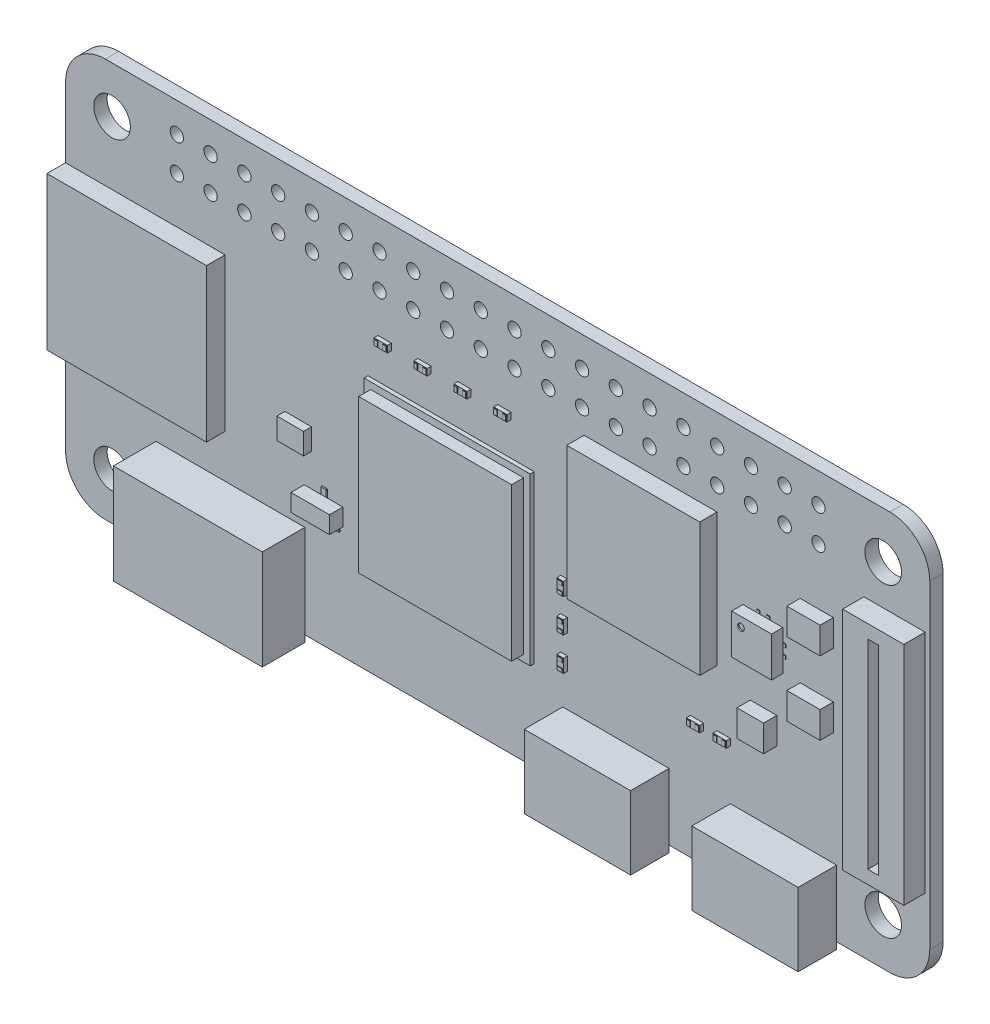
SolidWorks part; units mm, degrees
ref_plane "Front Plane" through (0, 0, 0) normal (0, 0, 1) x (1, 0, 0)
ref_plane "Top Plane" through (0, 0, 0) normal (0, 1, 0) x (1, 0, 0)
ref_plane "Right Plane" through (0, 0, 0) normal (1, 0, 0) x (0, 0, -1)
sketch "Sketch1" plane through (0, 0, 0) normal (0, 0, 1) x (1, 0, 0)
  line L0 (3, 0) -> (62, 0)
  line L1 (65, 3) -> (65, 27)
  line L2 (62, 30) -> (3, 30)
  line L3 (0, 27) -> (0, 3)
  arc A0 (62, 0) -> (65, 3) centre (62, 3) ccw
  arc A1 (65, 27) -> (62, 30) centre (62, 27) ccw
  arc A2 (3, 30) -> (0, 27) centre (3, 27) ccw
  arc A3 (0, 3) -> (3, 0) centre (3, 3) ccw
extrude "PCB" add sketch "Sketch1" along normal blind 1
ref_plane "Plane_z1" through (0, 0, 1) normal (0, 0, 1) x (1, 0, 0)
sketch "Sketch2" plane through (0, 0, 1) normal (0, 0, 1) x (1, 0, 0)
  line L1 (52, 15.3) -> (52.25, 15.3)
  line L2 (52, 15.3) -> (52, 15.6)
  line L3 (52, 15.6) -> (52.25, 15.6)
  line L4 (52.25, 15.3) -> (52.25, 15.6)
  line L6 (50.8, 16.5) -> (51.1, 16.5)
  line L7 (50.8, 16.5) -> (50.8, 16.75)
  line L8 (50.8, 16.75) -> (51.1, 16.75)
  line L9 (51.1, 16.5) -> (51.1, 16.75)
  line L11 (52, 18.4) -> (52.25, 18.4)
  line L12 (52, 18.4) -> (52, 18.7)
  line L13 (52, 18.7) -> (52.25, 18.7)
  line L14 (52.25, 18.4) -> (52.25, 18.7)
  line L16 (53.9, 16.5) -> (54.2, 16.5)
  line L17 (53.9, 16.5) -> (53.9, 16.75)
  line L18 (53.9, 16.75) -> (54.2, 16.75)
  line L19 (54.2, 16.5) -> (54.2, 16.75)
  line L21 (52.75, 15.3) -> (53, 15.3)
  line L22 (52.75, 15.3) -> (52.75, 15.6)
  line L23 (52.75, 15.6) -> (53, 15.6)
  line L24 (53, 15.3) -> (53, 15.6)
  line L26 (50.8, 17.25) -> (51.1, 17.25)
  line L27 (50.8, 17.25) -> (50.8, 17.5)
  line L28 (50.8, 17.5) -> (51.1, 17.5)
  line L29 (51.1, 17.25) -> (51.1, 17.5)
  line L31 (52.75, 18.4) -> (53, 18.4)
  line L32 (52.75, 18.4) -> (52.75, 18.7)
  line L33 (52.75, 18.7) -> (53, 18.7)
  line L34 (53, 18.4) -> (53, 18.7)
  line L36 (53.9, 17.25) -> (54.2, 17.25)
  line L37 (53.9, 17.25) -> (53.9, 17.5)
  line L38 (53.9, 17.5) -> (54.2, 17.5)
  line L39 (54.2, 17.25) -> (54.2, 17.5)
extrude "SMD_add00" add sketch "Sketch2" along normal blind 0.05
sketch "Sketch3" plane through (0, 0, 1) normal (0, 0, 1) x (1, 0, 0)
  line L1 (18.35, 8.05) -> (18.75, 8.05)
  line L2 (18.35, 8.05) -> (18.35, 8.75)
  line L3 (18.35, 8.75) -> (18.75, 8.75)
  line L4 (18.75, 8.05) -> (18.75, 8.75)
  line L6 (20.25, 8.05) -> (20.65, 8.05)
  line L7 (20.25, 8.05) -> (20.25, 8.75)
  line L8 (20.25, 8.75) -> (20.65, 8.75)
  line L9 (20.65, 8.05) -> (20.65, 8.75)
  line L11 (19.3, 9.65) -> (19.7, 9.65)
  line L12 (19.3, 9.65) -> (19.3, 10.35)
  line L13 (19.3, 10.35) -> (19.7, 10.35)
  line L14 (19.7, 9.65) -> (19.7, 10.35)
extrude "SMD_add01" add sketch "Sketch3" along normal blind 0.1
sketch "Sketch4" plane through (0, 0, 1) normal (0, 0, 1) x (1, 0, 0)
  line L1 (22.75, 6.75) -> (35.25, 6.75)
  line L2 (22.75, 6.75) -> (22.75, 19.25)
  line L3 (22.75, 19.25) -> (35.25, 19.25)
  line L4 (35.25, 6.75) -> (35.25, 19.25)
  line L6 (37.25, 7.5) -> (37.75, 7.5)
  line L7 (37.25, 7.5) -> (37.25, 8.5)
  line L8 (37.25, 8.5) -> (37.75, 8.5)
  line L9 (37.75, 7.5) -> (37.75, 8.5)
  line L11 (37.25, 10) -> (37.75, 10)
  line L12 (37.25, 10) -> (37.25, 11)
  line L13 (37.25, 11) -> (37.75, 11)
  line L14 (37.75, 10) -> (37.75, 11)
  line L16 (37.25, 12.5) -> (37.75, 12.5)
  line L17 (37.25, 12.5) -> (37.25, 13.5)
  line L18 (37.25, 13.5) -> (37.75, 13.5)
  line L19 (37.75, 12.5) -> (37.75, 13.5)
  line L21 (47, 8.75) -> (48, 8.75)
  line L22 (47, 8.75) -> (47, 9.25)
  line L23 (47, 9.25) -> (48, 9.25)
  line L24 (48, 8.75) -> (48, 9.25)
  line L26 (49, 8.75) -> (50, 8.75)
  line L27 (49, 8.75) -> (49, 9.25)
  line L28 (49, 9.25) -> (50, 9.25)
  line L29 (50, 8.75) -> (50, 9.25)
  line L31 (23.5, 21.75) -> (24.5, 21.75)
  line L32 (23.5, 21.75) -> (23.5, 22.25)
  line L33 (23.5, 22.25) -> (24.5, 22.25)
  line L34 (24.5, 21.75) -> (24.5, 22.25)
  line L36 (26.5, 21.75) -> (27.5, 21.75)
  line L37 (26.5, 21.75) -> (26.5, 22.25)
  line L38 (26.5, 22.25) -> (27.5, 22.25)
  line L39 (27.5, 21.75) -> (27.5, 22.25)
  line L41 (29.5, 21.75) -> (30.5, 21.75)
  line L42 (29.5, 21.75) -> (29.5, 22.25)
  line L43 (29.5, 22.25) -> (30.5, 22.25)
  line L44 (30.5, 21.75) -> (30.5, 22.25)
  line L46 (32.5, 21.75) -> (33.5, 21.75)
  line L47 (32.5, 21.75) -> (32.5, 22.25)
  line L48 (32.5, 22.25) -> (33.5, 22.25)
  line L49 (33.5, 21.75) -> (33.5, 22.25)
extrude "SMD_add02" add sketch "Sketch4" along normal blind 0.3
sketch "Sketch5" plane through (0, 0, 1) normal (0, 0, 1) x (1, 0, 0)
  line L1 (16.5, 12.2) -> (18.5, 12.2)
  line L2 (16.5, 12.2) -> (16.5, 13.8)
  line L3 (16.5, 13.8) -> (18.5, 13.8)
  line L4 (18.5, 12.2) -> (18.5, 13.8)
extrude "SMD_add03" add sketch "Sketch5" along normal blind 0.6
sketch "Sketch6" plane through (0, 0, 1) normal (0, 0, 1) x (1, 0, 0)
  line L1 (55.25, 19) -> (57.75, 19)
  line L2 (55.25, 19) -> (55.25, 21)
  line L3 (55.25, 21) -> (57.75, 21)
  line L4 (57.75, 19) -> (57.75, 21)
  line L6 (55.25, 13.5) -> (57.75, 13.5)
  line L7 (55.25, 13.5) -> (55.25, 15.5)
  line L8 (55.25, 15.5) -> (57.75, 15.5)
  line L9 (57.75, 13.5) -> (57.75, 15.5)
  line L11 (51.5, 10.5) -> (53.5, 10.5)
  line L12 (51.5, 10.5) -> (51.5, 12.5)
  line L13 (51.5, 12.5) -> (53.5, 12.5)
  line L14 (53.5, 10.5) -> (53.5, 12.5)
extrude "SMD_add04" add sketch "Sketch6" along normal blind 1
sketch "Sketch7" plane through (0, 0, 1) normal (0, 0, 1) x (1, 0, 0)
  line L1 (39, 13.5) -> (49, 13.5)
  line L2 (39, 13.5) -> (39, 23.5)
  line L3 (39, 23.5) -> (49, 23.5)
  line L4 (49, 13.5) -> (49, 23.5)
extrude "SMD_add05" add sketch "Sketch7" along normal blind 1.3
sketch "Sketch8" plane through (0, 0, 1) normal (0, 0, 1) x (1, 0, 0)
  line L1 (0, 10.25) -> (12, 10.25)
  line L2 (0, 10.25) -> (0, 21.75)
  line L3 (0, 21.75) -> (12, 21.75)
  line L4 (12, 10.25) -> (12, 21.75)
extrude "SMD_add06" add sketch "Sketch8" along normal blind 1.4
sketch "Sketch9" plane through (0, 0, 1) normal (0, 0, 1) x (1, 0, 0)
  line L1 (60.05, 6.5) -> (64.65, 6.5)
  line L2 (60.05, 6.5) -> (60.05, 23.5)
  line L3 (60.05, 23.5) -> (64.65, 23.5)
  line L4 (64.65, 6.5) -> (64.65, 23.5)
extrude "SMD_add07" add sketch "Sketch9" along normal blind 1.6
sketch "Sketch10" plane through (0, 0, 1) normal (0, 0, 1) x (1, 0, 0)
  line L1 (37.4, -0.5) -> (45.4, -0.5)
  line L2 (37.4, -0.5) -> (37.4, 5)
  line L3 (37.4, 5) -> (45.4, 5)
  line L4 (45.4, -0.5) -> (45.4, 5)
  line L6 (50, -0.5) -> (58, -0.5)
  line L7 (50, -0.5) -> (50, 5)
  line L8 (50, 5) -> (58, 5)
  line L9 (58, -0.5) -> (58, 5)
extrude "SMD_add08" add sketch "Sketch10" along normal blind 2.9
sketch "Sketch11" plane through (0, 0, 1) normal (0, 0, 1) x (1, 0, 0)
  line L1 (6.8, -0.5) -> (18, -0.5)
  line L2 (6.8, -0.5) -> (6.8, 7)
  line L3 (6.8, 7) -> (18, 7)
  line L4 (18, -0.5) -> (18, 7)
extrude "SMD_add09" add sketch "Sketch11" along normal blind 3.2
ref_plane "Plane_z1_05" through (0, 0, 1.05) normal (0, 0, 1) x (1, 0, 0)
sketch "Sketch12" plane through (0, 0, 1.05) normal (0, 0, 1) x (1, 0, 0)
  line L1 (51, 15.5) -> (54, 15.5)
  line L2 (51, 15.5) -> (51, 18.5)
  line L3 (51, 18.5) -> (54, 18.5)
  line L4 (54, 15.5) -> (54, 18.5)
extrude "SMD_add10" add sketch "Sketch12" along normal blind 0.85
ref_plane "Plane_z1_1" through (0, 0, 1.1) normal (0, 0, 1) x (1, 0, 0)
sketch "Sketch13" plane through (0, 0, 1.1) normal (0, 0, 1) x (1, 0, 0)
  line L1 (18.05, 8.55) -> (20.95, 8.55)
  line L2 (18.05, 8.55) -> (18.05, 9.85)
  line L3 (18.05, 9.85) -> (20.95, 9.85)
  line L4 (20.95, 8.55) -> (20.95, 9.85)
extrude "SMD_add11" add sketch "Sketch13" along normal blind 1
ref_plane "Plane_z1_3" through (0, 0, 1.3) normal (0, 0, 1) x (1, 0, 0)
sketch "Sketch14" plane through (0, 0, 1.3) normal (0, 0, 1) x (1, 0, 0)
  line L1 (37.3, 7.55) -> (37.7, 7.55)
  line L2 (37.3, 7.55) -> (37.3, 7.8)
  line L3 (37.3, 7.8) -> (37.7, 7.8)
  line L4 (37.7, 7.55) -> (37.7, 7.8)
  line L6 (37.3, 8.2) -> (37.7, 8.2)
  line L7 (37.3, 8.2) -> (37.3, 8.45)
  line L8 (37.3, 8.45) -> (37.7, 8.45)
  line L9 (37.7, 8.2) -> (37.7, 8.45)
  line L11 (37.3, 10.05) -> (37.7, 10.05)
  line L12 (37.3, 10.05) -> (37.3, 10.3)
  line L13 (37.3, 10.3) -> (37.7, 10.3)
  line L14 (37.7, 10.05) -> (37.7, 10.3)
  line L16 (37.3, 10.7) -> (37.7, 10.7)
  line L17 (37.3, 10.7) -> (37.3, 10.95)
  line L18 (37.3, 10.95) -> (37.7, 10.95)
  line L19 (37.7, 10.7) -> (37.7, 10.95)
  line L21 (37.3, 12.55) -> (37.7, 12.55)
  line L22 (37.3, 12.55) -> (37.3, 12.8)
  line L23 (37.3, 12.8) -> (37.7, 12.8)
  line L24 (37.7, 12.55) -> (37.7, 12.8)
  line L26 (37.3, 13.2) -> (37.7, 13.2)
  line L27 (37.3, 13.2) -> (37.3, 13.45)
  line L28 (37.3, 13.45) -> (37.7, 13.45)
  line L29 (37.7, 13.2) -> (37.7, 13.45)
  line L31 (47.05, 8.8) -> (47.3, 8.8)
  line L32 (47.05, 8.8) -> (47.05, 9.2)
  line L33 (47.05, 9.2) -> (47.3, 9.2)
  line L34 (47.3, 8.8) -> (47.3, 9.2)
  line L36 (47.7, 8.8) -> (47.95, 8.8)
  line L37 (47.7, 8.8) -> (47.7, 9.2)
  line L38 (47.7, 9.2) -> (47.95, 9.2)
  line L39 (47.95, 8.8) -> (47.95, 9.2)
  line L41 (49.05, 8.8) -> (49.3, 8.8)
  line L42 (49.05, 8.8) -> (49.05, 9.2)
  line L43 (49.05, 9.2) -> (49.3, 9.2)
  line L44 (49.3, 8.8) -> (49.3, 9.2)
  line L46 (49.7, 8.8) -> (49.95, 8.8)
  line L47 (49.7, 8.8) -> (49.7, 9.2)
  line L48 (49.7, 9.2) -> (49.95, 9.2)
  line L49 (49.95, 8.8) -> (49.95, 9.2)
  line L51 (23.55, 21.8) -> (23.8, 21.8)
  line L52 (23.55, 21.8) -> (23.55, 22.2)
  line L53 (23.55, 22.2) -> (23.8, 22.2)
  line L54 (23.8, 21.8) -> (23.8, 22.2)
  line L56 (24.2, 21.8) -> (24.45, 21.8)
  line L57 (24.2, 21.8) -> (24.2, 22.2)
  line L58 (24.2, 22.2) -> (24.45, 22.2)
  line L59 (24.45, 21.8) -> (24.45, 22.2)
  line L61 (26.55, 21.8) -> (26.8, 21.8)
  line L62 (26.55, 21.8) -> (26.55, 22.2)
  line L63 (26.55, 22.2) -> (26.8, 22.2)
  line L64 (26.8, 21.8) -> (26.8, 22.2)
  line L66 (27.2, 21.8) -> (27.45, 21.8)
  line L67 (27.2, 21.8) -> (27.2, 22.2)
  line L68 (27.2, 22.2) -> (27.45, 22.2)
  line L69 (27.45, 21.8) -> (27.45, 22.2)
  line L71 (29.55, 21.8) -> (29.8, 21.8)
  line L72 (29.55, 21.8) -> (29.55, 22.2)
  line L73 (29.55, 22.2) -> (29.8, 22.2)
  line L74 (29.8, 21.8) -> (29.8, 22.2)
  line L76 (30.2, 21.8) -> (30.45, 21.8)
  line L77 (30.2, 21.8) -> (30.2, 22.2)
  line L78 (30.2, 22.2) -> (30.45, 22.2)
  line L79 (30.45, 21.8) -> (30.45, 22.2)
  line L81 (32.55, 21.8) -> (32.8, 21.8)
  line L82 (32.55, 21.8) -> (32.55, 22.2)
  line L83 (32.55, 22.2) -> (32.8, 22.2)
  line L84 (32.8, 21.8) -> (32.8, 22.2)
  line L86 (33.2, 21.8) -> (33.45, 21.8)
  line L87 (33.2, 21.8) -> (33.2, 22.2)
  line L88 (33.2, 22.2) -> (33.45, 22.2)
  line L89 (33.45, 21.8) -> (33.45, 22.2)
extrude "SMD_add12" add sketch "Sketch14" along normal blind 0.05
sketch "Sketch15" plane through (0, 0, 1.3) normal (0, 0, 1) x (1, 0, 0)
  line L1 (23.25, 7.25) -> (34.75, 7.25)
  line L2 (23.25, 7.25) -> (23.25, 18.75)
  line L3 (23.25, 18.75) -> (34.75, 18.75)
  line L4 (34.75, 7.25) -> (34.75, 18.75)
extrude "SMD_add13" add sketch "Sketch15" along normal blind 0.9
ref_plane "Plane_y6_5" through (0, 6.5, 0) normal (0, 1, 0) x (1, 0, 0)
sketch "Sketch16" plane through (0, 6.5, 0) normal (0, 1, 0) x (1, 0, 0)
  line L1 (9.65, -1.6) -> (15.15, -1.6)
  line L2 (9.65, -1.6) -> (9.65, -3.6)
  line L3 (9.65, -3.6) -> (15.15, -3.6)
  line L4 (15.15, -1.6) -> (15.15, -3.6)
extrude "SMD_cut00" cut sketch "Sketch16" against normal blind 7
ref_plane "Plane_z1_9" through (0, 0, 1.9) normal (0, 0, 1) x (1, 0, 0)
sketch "Sketch17" plane through (0, 0, 1.9) normal (0, 0, 1) x (1, 0, 0)
  circle A0 centre (51.7, 17.8) radius 0.25
extrude "SMD_cut01" cut sketch "Sketch17" against normal blind 0.1
ref_plane "Plane_z2_6" through (0, 0, 2.6) normal (0, 0, 1) x (1, 0, 0)
sketch "Sketch18" plane through (0, 0, 2.6) normal (0, 0, 1) x (1, 0, 0)
  line L1 (61.95, 7.5) -> (62.75, 7.5)
  line L2 (61.95, 7.5) -> (61.95, 22.5)
  line L3 (61.95, 22.5) -> (62.75, 22.5)
  line L4 (62.75, 7.5) -> (62.75, 22.5)
extrude "SMD_cut02" cut sketch "Sketch18" against normal blind 1.1
sketch "Sketch19" plane through (0, 0, 1) normal (0, 0, 1) x (1, 0, 0)
  circle A0 centre (3.5, 3.5) radius 1.375
  circle A1 centre (61.5, 3.5) radius 1.375
  circle A2 centre (3.5, 26.5) radius 1.375
  circle A3 centre (61.5, 26.5) radius 1.375
  circle A4 centre (8.37, 25.23) radius 0.5
  circle A5 centre (8.37, 27.77) radius 0.5
  circle A6 centre (10.91, 25.23) radius 0.5
  circle A7 centre (10.91, 27.77) radius 0.5
  circle A8 centre (13.45, 25.23) radius 0.5
  circle A9 centre (13.45, 27.77) radius 0.5
  circle A10 centre (15.99, 25.23) radius 0.5
  circle A11 centre (15.99, 27.77) radius 0.5
  circle A12 centre (18.53, 25.23) radius 0.5
  circle A13 centre (18.53, 27.77) radius 0.5
  circle A14 centre (21.07, 25.23) radius 0.5
  circle A15 centre (21.07, 27.77) radius 0.5
  circle A16 centre (23.61, 25.23) radius 0.5
  circle A17 centre (23.61, 27.77) radius 0.5
  circle A18 centre (26.15, 25.23) radius 0.5
  circle A19 centre (26.15, 27.77) radius 0.5
  circle A20 centre (28.69, 25.23) radius 0.5
  circle A21 centre (28.69, 27.77) radius 0.5
  circle A22 centre (31.23, 25.23) radius 0.5
  circle A23 centre (31.23, 27.77) radius 0.5
  circle A24 centre (33.77, 25.23) radius 0.5
  circle A25 centre (33.77, 27.77) radius 0.5
  circle A26 centre (36.31, 25.23) radius 0.5
  circle A27 centre (36.31, 27.77) radius 0.5
  circle A28 centre (38.85, 25.23) radius 0.5
  circle A29 centre (38.85, 27.77) radius 0.5
  circle A30 centre (41.39, 25.23) radius 0.5
  circle A31 centre (41.39, 27.77) radius 0.5
  circle A32 centre (43.93, 25.23) radius 0.5
  circle A33 centre (43.93, 27.77) radius 0.5
  circle A34 centre (46.47, 25.23) radius 0.5
  circle A35 centre (46.47, 27.77) radius 0.5
  circle A36 centre (49.01, 25.23) radius 0.5
  circle A37 centre (49.01, 27.77) radius 0.5
  circle A38 centre (51.55, 25.23) radius 0.5
  circle A39 centre (51.55, 27.77) radius 0.5
  circle A40 centre (54.09, 25.23) radius 0.5
  circle A41 centre (54.09, 27.77) radius 0.5
  circle A42 centre (56.63, 25.23) radius 0.5
  circle A43 centre (56.63, 27.77) radius 0.5
extrude "Holes" cut sketch "Sketch19" against normal blind 1
equation "\"pcb_t\" = 1.0mm"
equation "\"D1@PCB\" = \"pcb_t\""
